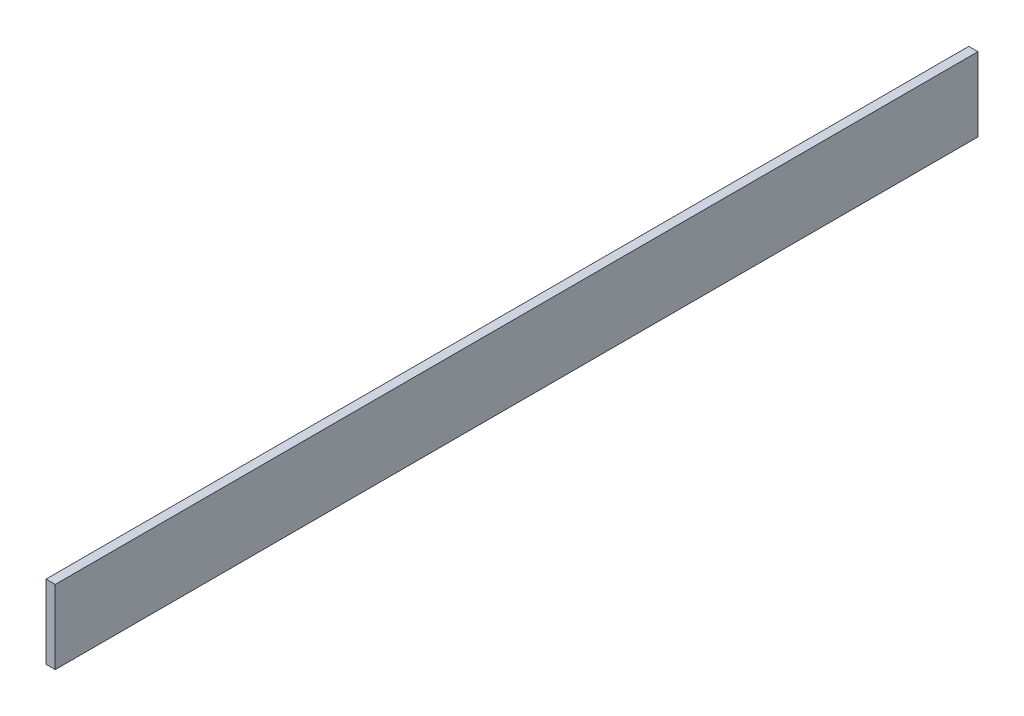
SolidWorks part; units mm, degrees
ref_plane "Front Plane" through (0, 0, 0) normal (0, 0, 1) x (1, 0, 0)
ref_plane "Top Plane" through (0, 0, 0) normal (0, 1, 0) x (1, 0, 0)
ref_plane "Right Plane" through (0, 0, 0) normal (1, 0, 0) x (0, 0, -1)
sketch "Sketch1" plane through (0, 0, 0) normal (1, 0, 0) x (0, 0, -1)
  line L1 (-635, -50.8) -> (635, -50.8)
  line L2 (-635, -50.8) -> (-635, 50.8)
  line L3 (-635, 50.8) -> (635, 50.8)
  line L4 (635, -50.8) -> (635, 50.8)
  line L5 (-635, -50.8) -> (635, 50.8) construction
  line L6 (-635, 50.8) -> (635, -50.8) construction
  point P0 (0, 0)
  dimension "D1" = 101.6
  dimension "D2" = 1270
extrude "Boss-Extrude1" add sketch "Sketch1" along normal blind 12.7
